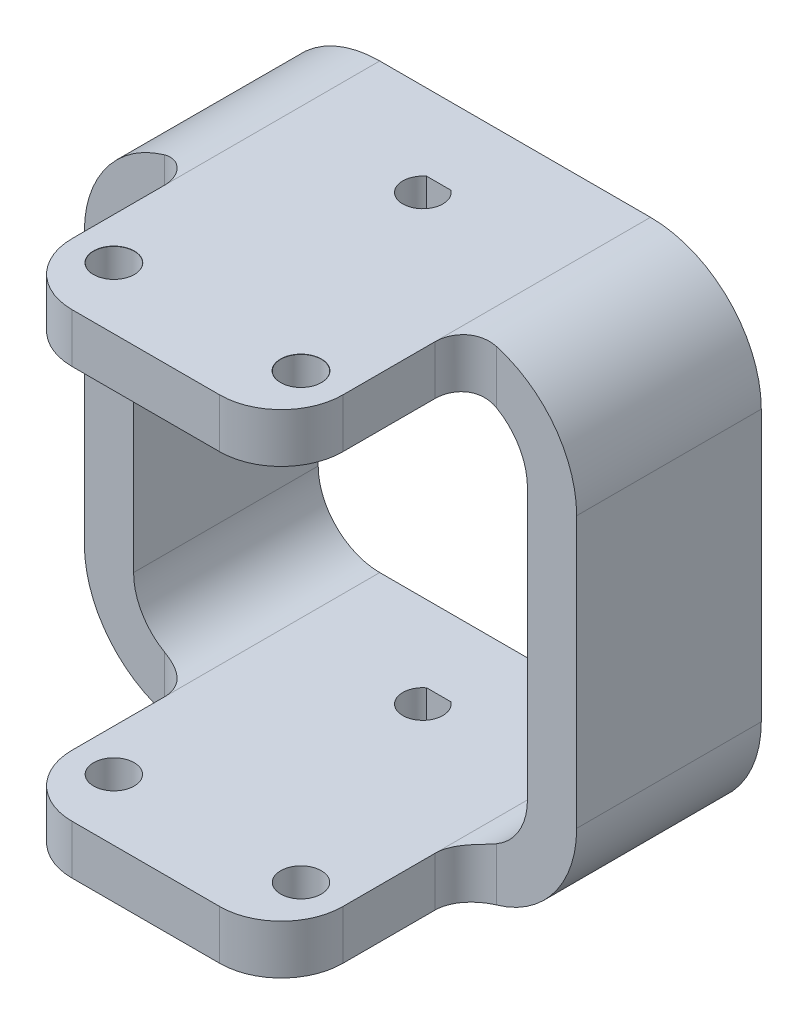
SolidWorks part; units mm, degrees
material "Plastique personnalisé"
ref_plane "Plan de face" through (0, 0, 0) normal (0, 0, 1) x (1, 0, 0)
ref_plane "Plan de dessus" through (0, 0, 0) normal (0, 1, 0) x (1, 0, 0)
ref_plane "Plan de droite" through (0, 0, 0) normal (1, 0, 0) x (0, 0, -1)
sketch "Esquisse1" plane through (0, 0, 0) normal (0, 0, 1) x (1, 0, 0)
  line L1 (40, -40) -> (-40, -40)
  line L2 (40, -40) -> (40, 40)
  line L3 (40, 40) -> (-40, 40)
  line L4 (-40, -40) -> (-40, 40)
  line L5 (40, -40) -> (-40, 40) construction
  line L6 (40, 40) -> (-40, -40) construction
  line L7 (-32, -32) -> (32, -32)
  line L8 (-32, -32) -> (-32, 32)
  line L9 (-32, 32) -> (32, 32)
  line L10 (32, -32) -> (32, 32)
  line L11 (-32, -32) -> (32, 32) construction
  line L12 (-32, 32) -> (32, -32) construction
  point P0 (0, 0)
  point P11 (0, 0)
  dimension "D1" = 8
  dimension "D3" = 80
extrude "Boss.-Extru.1" add sketch "Esquisse1" along normal mid plane 30
sketch "Esquisse2" plane through (0, 0, 0) normal (1, 0, 0) x (0, 0, -1)
  circle A0 centre (0, 0) radius 5
  dimension "D1" = 10
extrude "Enlèv. mat.-Extru.1" [suppressed] cut sketch "Esquisse2" against normal through all both and the other way through all
sketch "Esquisse3" plane through (0, -40, 0) normal (0, -1, 0) x (-1, 0, 0)
  circle A0 centre (0, 0) radius 5
  dimension "D1" = 10
extrude "Boss.-Extru.2" [suppressed] add sketch "Esquisse3" along normal blind 20
mirror "Symétrie1" [suppressed] about plane through (0, 0, 0) normal (0, 1, 0)
fillet "Congé2" radius 18 4 edges at (40, -40, 0) (-40, -40, 0) (-40, 40, 0) (40, 40, 0)
fillet "Congé3" radius 10 4 edges at (-32, 32, 0) (-32, -32, 0) (32, -32, 0) (32, 32, 0)
sketch "Esquisse5" [suppressed] plane through (0, -60, 0) normal (0, -1, 0) x (1, 0, 0)
  circle A0 centre (0, 0) radius 3
  circle A1 centre (0, 0) radius 5 construction
  dimension "D1" = 6
extrude "Boss.-Extru.3" [suppressed] add sketch "Esquisse5" along normal blind 15
sketch "Esquisse6" [suppressed] plane through (0, -75, 0) normal (0, -1, 0) x (1, 0, 0)
  line L1 (3, -3) -> (-3, -3)
  line L2 (3, -3) -> (3, -1.8)
  line L3 (3, -1.8) -> (-3, -1.8)
  line L4 (-3, -3) -> (-3, -1.8)
  circle A0 centre (0, 0) radius 3 construction
  dimension "D1" = 1.2
extrude "Enlèv. mat.-Extru.2" [suppressed] cut sketch "Esquisse6" against normal up to surface (15 mm away) contours L1 L4 L3 L2 up to face at (0, -40, 0)
sketch "Esquisse7" plane through (0, 0, 15) normal (0, 0, 1) x (1, 0, 0)
  line L0 (22, 40) -> (-22, 40) construction
  line L1 (22, 32) -> (-22, 32)
  line L2 (22, 32) -> (22, 40)
  line L3 (22, 40) -> (-22, 40)
  line L4 (-22, 32) -> (-22, 40)
  line L6 (22, 32) -> (-22, 32) construction
extrude "Boss.-Extru.4" add sketch "Esquisse7" along normal blind 30
hole_wizard "Dégagement M61" positions "Esquisse10" profile "Esquisse9" hole size "M6" standard "Ansi Metric" end condition through all
sketch "Esquisse10" plane through (0, 40, 0) normal (0, -1, 0) x (0, 0, -1)
  line L0 (-35, 15.205) -> (-35, -15.205) construction
  line L3 (-35, 0) -> (-45, 0) construction
  line L6 (-45, 22) -> (-45, -22) construction
  point P0 (-35, 15.205)
  point P2 (-35, -15.205)
  point P20 (-45, 0)
  dimension "D1" = 30.41
  dimension "D2" = 10
sketch "Esquisse9" plane through (15.205, 40, 35) normal (1, 0, 0) x (0, 0, 1)
  line L0 (0, 0) -> (0, 80)
  line L1 (0, 80) -> (3.3, 80)
  line L2 (3.3, 80) -> (3.3, 0.025)
  line L3 (3.3, 0.025) -> (3.325, 0)
  line L5 (3.325, 0) -> (0, 0)
  line L6 (-3.3, 0.025) -> (-3.325, 0) construction
  line L11 (0, -6.35) -> (0, 107.95) construction
  dimension "Diamètre du perçage jusqu'au prochain" = 6.6
  dimension "Profondeur du perçage jusqu'au prochain" = 80
  dimension "Diamètre du fraisage entrant" = 6.65
  dimension "Angle du fraisage entrant" = 90
fillet "Congé1" radius 10 2 edges at (22, 36, 45) (-22, 36, 45)
mirror "Symétrie2" about plane through (0, 0, 0) normal (0, 1, 0) of "Boss.-Extru.4", "Dégagement M61", "Congé1"
fillet "Congé4" radius 5 4 edges at (-22, -36, 15) (-22, 36, 15) (22, -36, 15) (22, 36, 15)
sketch "Esquisse11" plane through (0, -40, -40) normal (0, 1, 0) x (1, 0, 0)
  line L0 (40, -40) -> (-40, -40) construction
  line L1 (40, -25) -> (40, -55) construction
  line L2 (-40, -55) -> (-40, -25) construction
  line L3 (1.9649, -37.405) -> (-1.9649, -37.405)
  arc A0 (-1.9649, -37.405) -> (1.9649, -37.405) centre (0, -40) ccw
  dimension "D1" = 6.51
  dimension "D2" = 5.85
extrude "Enlèv. mat.-Extru.3" cut sketch "Esquisse11" along normal through all
